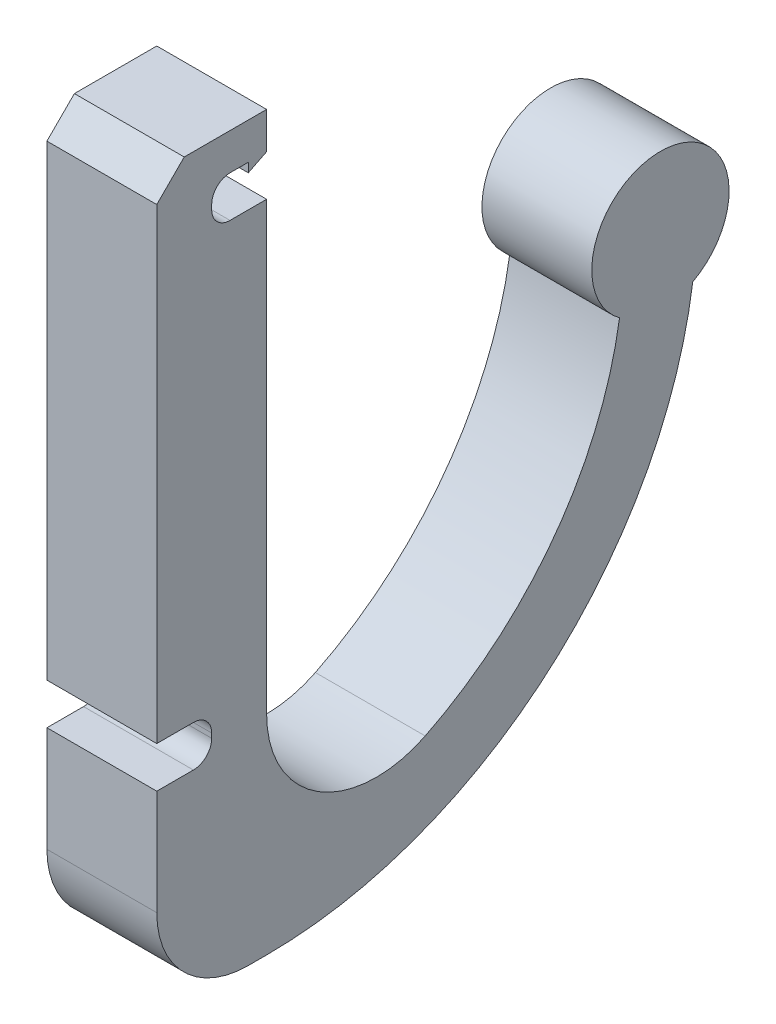
SolidWorks part; units mm, degrees
ref_plane "Front Plane" through (0, 0, 0) normal (0, 0, 1) x (1, 0, 0)
ref_plane "Top Plane" through (0, 0, 0) normal (0, 1, 0) x (1, 0, 0)
ref_plane "Right Plane" through (0, 0, 0) normal (1, 0, 0) x (0, 0, -1)
sketch "Sketch2" plane through (0, 0, 0) normal (1, 0, 0) x (0, 0, -1)
  line L1 (-6, 40) -> (6, 40)
  line L2 (-6, 40) -> (-6, -40)
  line L3 (-6, -40) -> (6, -40)
  line L4 (6, 40) -> (6, -32)
  arc A0 (52.5577, 0.4093) -> (44.5577, 1.0014) centre (49.0254, 7.0254) ccw
  arc A2 (6, -32) -> (44.5577, 1.0014) centre (6, 7.0254) ccw
  arc A3 (6, -40) -> (52.5577, 0.4093) centre (6, 7.0254) ccw
  point P0 (0, 0)
  dimension "D3" = 15
  dimension "D1" = 80
  dimension "D2" = 12
extrude "Boss-Extrude1" add sketch "Sketch2" along normal blind 12
fillet "Fillet1" radius 12 1 edges at (6, -32, -6)
fillet "Fillet2" radius 10 1 edges at (6, -40, 6)
sketch "Sketch3" plane through (12, 0, 0) normal (1, 0, 0) x (0, 0, -1)
  line L0 (-6, 40) -> (-6, -30) construction
  line L1 (-6, -14) -> (0, -14)
  line L2 (-6, -14) -> (-6, -18.5)
  line L3 (-6, -18.5) -> (0, -18.5)
  line L4 (0, -14) -> (0, -18.5)
  line L5 (6, -17.1897) -> (6, 40) construction
  line L6 (6, 36) -> (0, 36)
  line L7 (6, 36) -> (6, 31.5)
  line L8 (6, 31.5) -> (0, 31.5)
  line L9 (0, 36) -> (0, 31.5)
  line L10 (6, 40) -> (-6, 40) construction
  dimension "D1" = 4.5
  dimension "D2" = 4.5
  dimension "D3" = 45.5
  dimension "D4" = 4
extrude "Cut-Extrude1" cut sketch "Sketch3" against normal blind 12
fillet "Fillet3" radius 2 4 edges at (6, 36, 0) (6, 31.5, 0) (6, -18.5, 0) (6, -14, 0)
chamfer "Chamfer1" distance 3 angle 45 1 edges at (6, 40, 6)
sketch "Sketch4" plane through (12, 0, 0) normal (1, 0, 0) x (0, 0, -1)
  line L0 (4, 36) -> (4, 35)
  line L1 (6, 36) -> (2, 36) construction
  line L2 (4, 35) -> (6, 36)
  line L3 (6, 36) -> (6, 40) construction
  line L4 (6, 36) -> (4, 36)
  dimension "D1" = 1
extrude "Boss-Extrude2" add sketch "Sketch4" against normal blind 12
